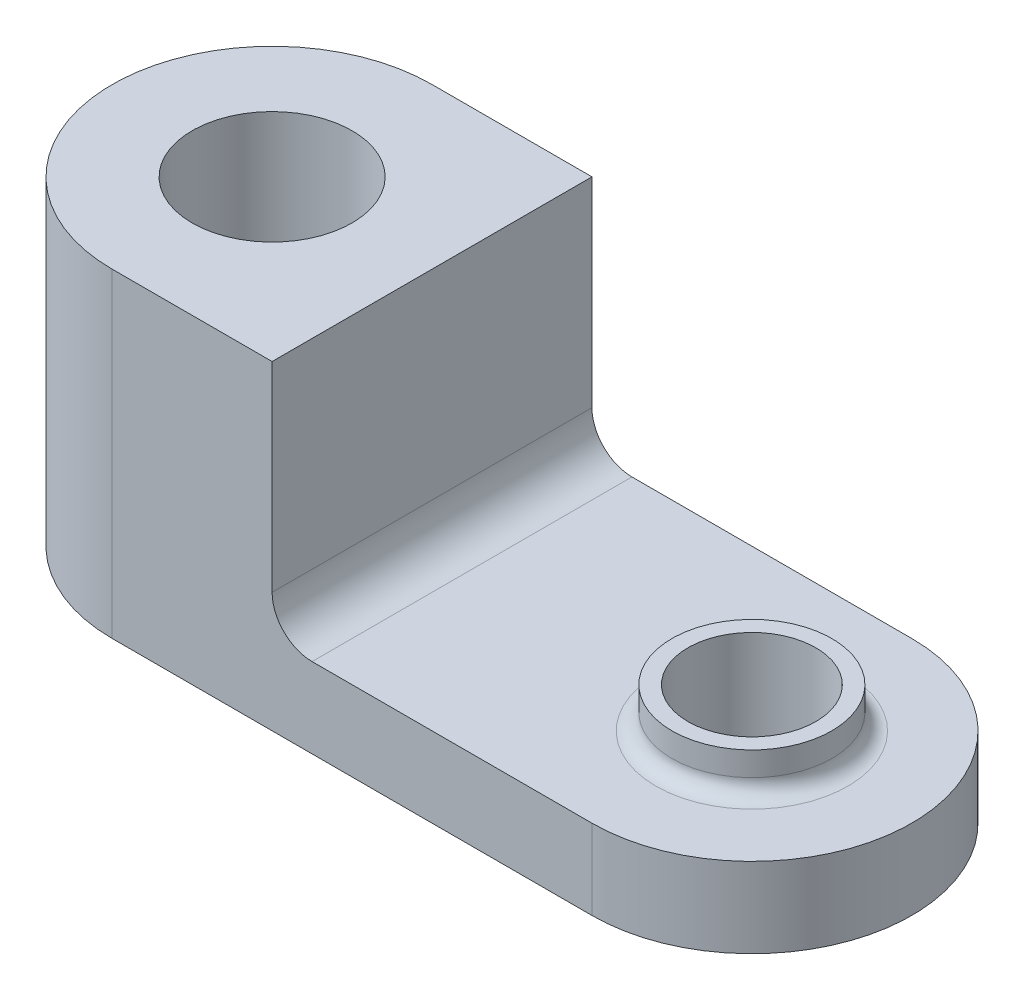
SolidWorks part; units mm, degrees
ref_plane "Front Plane" through (0, 0, 0) normal (0, 0, 1) x (1, 0, 0)
ref_plane "Top Plane" through (0, 0, 0) normal (0, 1, 0) x (1, 0, 0)
ref_plane "Right Plane" through (0, 0, 0) normal (1, 0, 0) x (0, 0, -1)
sketch "Sketch1" plane through (0, 0, 0) normal (0, 1, 0) x (1, 0, 0)
  line L0 (-60, 0) -> (60, 0) construction
  line L1 (0, -34.1934) -> (0, 34.1934) construction
  line L2 (0, 20) -> (60, 20)
  line L3 (20, 20) -> (20, -20)
  line L4 (60, -20) -> (0, -20)
  circle A0 centre (0, 0) radius 10
  arc A1 (0, 20) -> (0, -20) centre (0, 0) ccw
  circle A3 centre (60, 0) radius 10
  arc A4 (60, -20) -> (60, 20) centre (60, 0) ccw
  circle A5 centre (60, 0) radius 8
  point P7 (0, 0)
  point P13 (0, 0)
  dimension "D2" = 20
  dimension "D4" = 40
  dimension "D5" = 20
  dimension "D6" = 16
  dimension "D7" = 60
  dimension "D3" = 60
  dimension "D8" = 60
  dimension "D9" = 20
extrude "Boss-Extrude1" add sketch "Sketch1" along normal blind 10 contours L4 A4 L2 L3 A3 region at (46.0687, 0, 0)
extrude "Boss-Extrude2" add sketch "Sketch1<4>" along normal blind 15 contours A3 A5 region at (50.2828, 0, 0)
sketch "Sketch1<4>" plane through (0, 0, 0) normal (0, 1, 0) x (1, 0, 0) same geometry as "Sketch1"
extrude "Boss-Extrude3" add sketch "Sketch1<5>" along normal blind 40 contours L2 A1 L4 L3 A0 region at (10, 0, -19.4343)
sketch "Sketch1<5>" plane through (0, 0, 0) normal (0, 1, 0) x (1, 0, 0) same geometry as "Sketch1"
fillet "Fillet1" radius 5 1 edges at (20, 10, 0)
fillet "Fillet2" radius 2 1 edges at (60, 10, 10)
